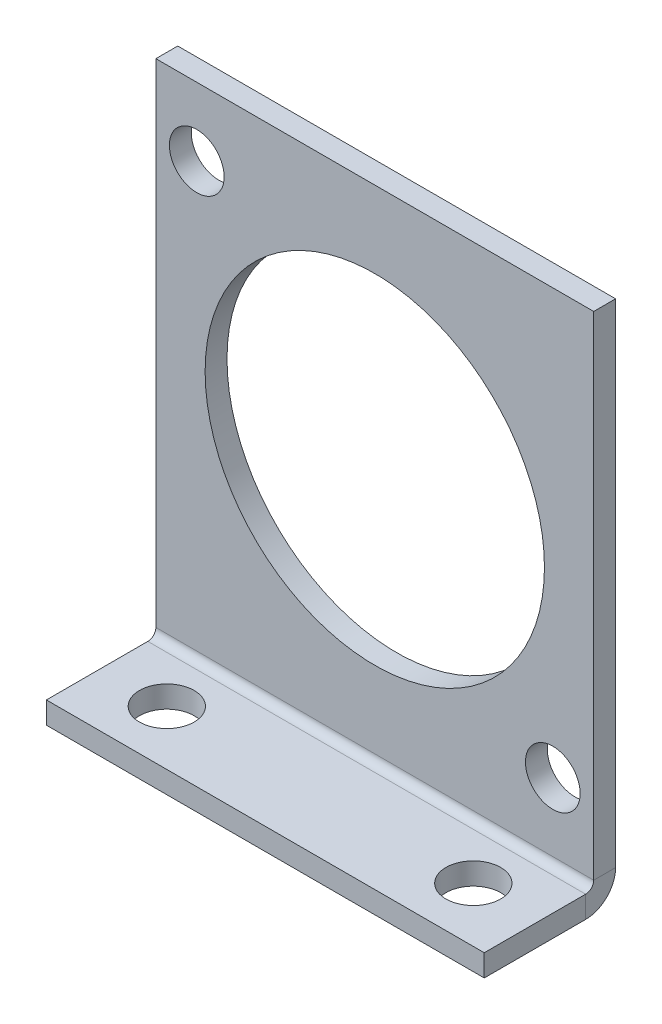
SolidWorks part; units mm, degrees
note: The reader was unsure of these and kept them because the rebuilt part matched: flange length of "Edge-Flange1".
material "1.0037 (S235JR)"
ref_plane "Front Plane" through (0, 0, 0) normal (0, 0, 1) x (1, 0, 0)
ref_plane "Top Plane" through (0, 0, 0) normal (0, 1, 0) x (1, 0, 0)
ref_plane "Right Plane" through (0, 0, 0) normal (1, 0, 0) x (0, 0, -1)
sketch "Sketch1" plane through (0, 0, 0) normal (0, 0, 1) x (1, 0, 0)
  line L1 (-20, 22.5) -> (20, 22.5)
  line L2 (-20, 22.5) -> (-20, -22.5)
  line L3 (-20, -22.5) -> (20, -22.5)
  line L4 (20, 22.5) -> (20, -22.5)
  line L5 (-20, 22.5) -> (20, -22.5) construction
  line L6 (-20, -22.5) -> (20, 22.5) construction
  point P0 (0, 0)
  dimension "D1" = 40
  dimension "D2" = 45
base flange "Base-Flange1" sketch "Sketch1" thickness 2 reverse thickness direction no parameters "D1"=0.7366
sketch "Sketch8" plane through (0, 0, 0) normal (0, 0, 1) x (1, 0, 0)
  circle A0 centre (0, 0) radius 15.5
  dimension "D1" = 31
extrude "Cut-Extrude5" cut sketch "Sketch8" against normal through all normal cut yes
sketch "Sketch9" plane through (0, 0, 0) normal (0, 0, 1) x (1, 0, 0)
  line L0 (0, 0) -> (-22.2359, 22.2359) construction
  line L1 (-22.2359, 22.2359) -> (24.9834, -24.9834) construction
  circle A0 centre (-16.2635, 16.2635) radius 2.5
  circle A1 centre (16.2635, -16.2635) radius 2.5
  dimension "D1" = 5
  dimension "D4" = 5
  dimension "D2" = 23
  dimension "D3" = 23
extrude "Cut-Extrude6" cut sketch "Sketch9" against normal through all normal cut yes
edge flange "Edge-Flange1" sketch "Sketch12" flange angle 90 flange length 12 flange position bend outside bend radius 0.7366 thickness 2 relief rectangular parameters "D6"=10
sketch "Sketch12" plane through (0, -22.5, 0) normal (0, 1, 0) x (-1, 0, 0)
  line L2 (-20, 0) -> (-20, 10)
  line L3 (-20, 10) -> (20, 10)
  line L4 (20, 10) -> (20, 0)
  line L5 (20, 0) -> (-20, 0) construction
  line L6 (20, 0) -> (-20, 0)
bend "EdgeBend1" bend radius 0.7366 bend angle 90 parameters "D5"=1
sketch "Sketch13" plane through (0, -25.2366, 0) normal (0, -1, 0) x (1, 0, 0)
  line L0 (-20, 0.7366) -> (-20, 10) construction
  line L1 (20, 10) -> (20, 0.7366) construction
  line L2 (-20, 10) -> (20, 10) construction
  circle A0 centre (-14, 5) radius 2.5
  circle A1 centre (14, 5) radius 2.5
  dimension "D1" = 5
  dimension "D2" = 5
  dimension "D3" = 6
  dimension "D4" = 6
  dimension "D5" = 5
  dimension "D6" = 5
extrude "Cut-Extrude7" cut sketch "Sketch13" against normal through all normal cut yes
sketch "Bend-Lines1" [suppressed] plane through (0, 0, 0) normal (0, 1, 0) x (1, 0, 0)
sketch "Bounding-Box1" [suppressed] plane through (0, 0, 0) normal (0, 1, 0) x (1, 0, 0)
sheet metal parameters "Sheet-Metal4" thickness 2 parameters "D1"=0.7366
flat pattern "Flat-Pattern4" [suppressed]
sketch "Bend-Lines2" plane through (0, 0, 0) normal (0, 1, 0) x (1, 0, 0)
sketch "Bounding-Box2" [suppressed] plane through (0, 0, 0) normal (0, 1, 0) x (1, 0, 0)
sheet metal parameters "Sheet-Metal7" thickness 2 parameters "D1"=0.7366
flat pattern "Flat-Pattern4"
sketch "Bend-Lines2" plane through (0, 0, 0) normal (0, 1, 0) x (1, 0, 0)
sketch "Bounding-Box2" [suppressed] plane through (0, 0, 0) normal (0, 1, 0) x (1, 0, 0)
sheet metal parameters "Sheet-Metal8" thickness 2 parameters "D1"=0.7366
flat pattern "Flat-Pattern4"
sketch "Bend-Lines2" plane through (0, 0, 0) normal (0, 1, 0) x (1, 0, 0)
sketch "Bounding-Box2" [suppressed] plane through (0, 0, 0) normal (0, 1, 0) x (1, 0, 0)
sheet metal parameters "Sheet-Metal9" thickness 2 parameters "D1"=0.7366
flat pattern "Flat-Pattern4" [suppressed]
sketch "Bend-Lines2" plane through (0, 0, 0) normal (0, 1, 0) x (1, 0, 0)
sketch "Bounding-Box2" [suppressed] plane through (0, 0, 0) normal (0, 1, 0) x (1, 0, 0)
bend of the flat pattern "Flatten-<EdgeBend1>1"
sheet metal parameters "Sheet-Metal10" thickness 2 parameters "D1"=0.7366
flat pattern "Flat-Pattern4"
sketch "Bend-Lines2" plane through (0, 0, 0) normal (0, 0, 1) x (1, 0, 0)
  line L0 (-20, -23.8639) -> (20, -23.8639) construction
  line L1 (-20, -23.8639) -> (20, -23.8639) construction
sketch3d "Bounding-Box2" [suppressed]
  line L0 (20, 22.5, 0) -> (20, -34.4912, 0) construction
  line L1 (-20, 22.5, 0) -> (-20, -34.4912, 0) construction
  line L2 (20, 22.5, 0) -> (-20, 22.5, 0) construction
  line L3 (20, -34.4912, 0) -> (-20, -34.4912, 0) construction
bend of the flat pattern "Flatten-<EdgeBend1>1"
